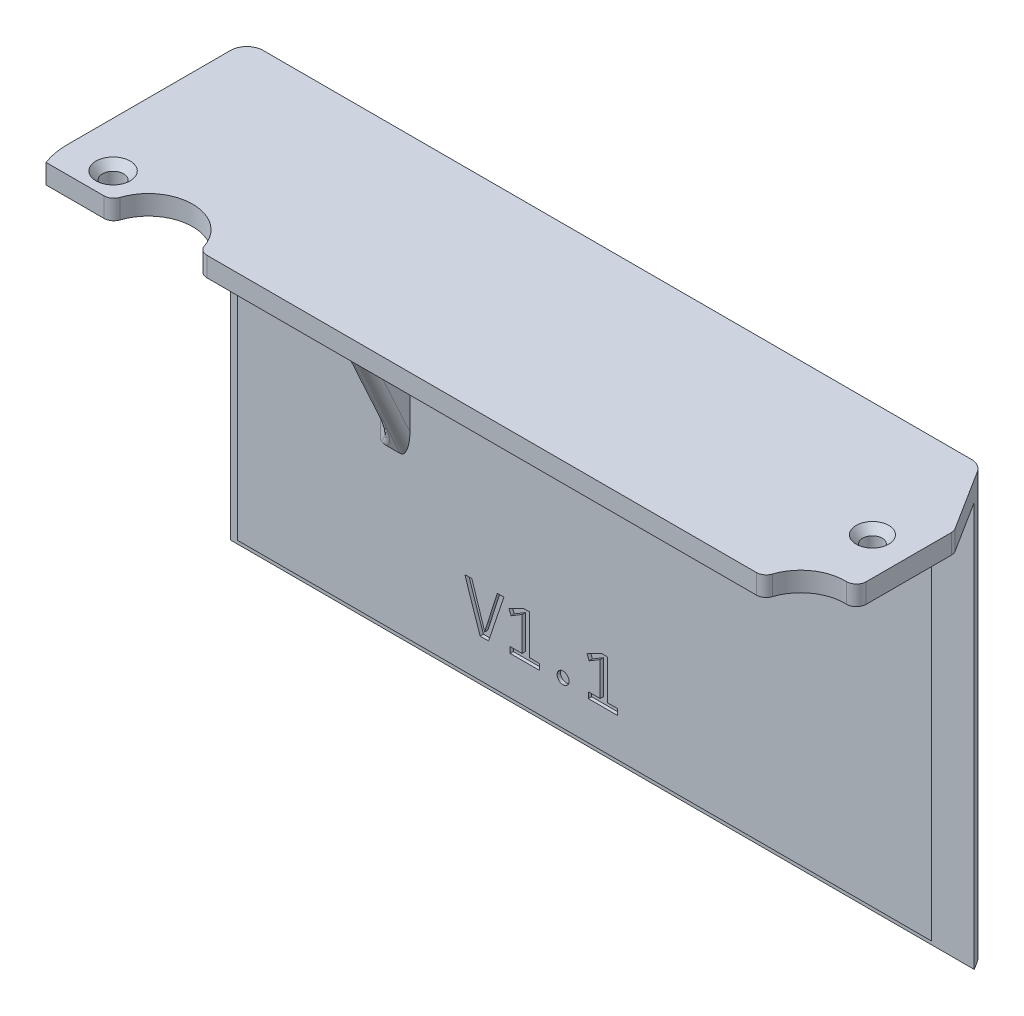
SolidWorks part; units mm, degrees
ref_plane "Front Plane" through (0, 0, 0) normal (0, 0, 1) x (1, 0, 0)
ref_plane "Top Plane" through (0, 0, 0) normal (0, 1, 0) x (1, 0, 0)
ref_plane "Right Plane" through (0, 0, 0) normal (1, 0, 0) x (0, 0, -1)
sketch "Sketch1" plane through (0, 0, 0) normal (0, 0, 1) x (1, 0, 0)
  line L1 (0, 0) -> (114, 0)
  line L2 (0, 0) -> (0, 65)
  line L3 (0, 65) -> (114, 65)
  line L4 (114, 0) -> (114, 65)
  dimension "D1" = 114
  dimension "D2" = 65
extrude "Boss-Extrude1" add sketch "Sketch1" along normal blind 2.5
sketch "Sketch2" plane through (0, 65, 0) normal (0, 1, 0) x (1, 0, 0)
  line L1 (114, -2.5) -> (0, -2.5) construction
  line L2 (110.2, -5) -> (3.3, -5)
  line L3 (3.3, -5) -> (5.8, -2.5)
  line L4 (107.7, -2.5) -> (110.2, -5)
  line L8 (5.8, -2.5) -> (107.7, -2.5)
  line L9 (0, -2.5) -> (0, 0) construction
  dimension "D1" = 2.5
  dimension "D3" = 45
  dimension "D4" = 45
  dimension "D5" = 5.8
  dimension "D6" = 6.3
extrude "Boss-Extrude2" add sketch "Sketch2" against normal offset from surface (62 mm away) 3 up to face at (57, 0, 1.25)
sketch "Sketch14" plane through (0, 65, 0) normal (0, 1, 0) x (1, 0, 0)
  line L0 (5.8, -2.5) -> (6.0828, -2.5)
  line L1 (6.0828, -2.5) -> (3.5828, -5)
  line L2 (3.3, -5) -> (110.2, -5) construction
  line L3 (3.5828, -5) -> (3.3, -5)
  line L4 (3.3, -5) -> (5.8, -2.5)
  line L5 (107.7, -2.5) -> (107.4172, -2.5)
  line L6 (107.4172, -2.5) -> (109.9172, -5)
  line L7 (109.9172, -5) -> (110.2, -5)
  line L8 (110.2, -5) -> (107.7, -2.5)
  dimension "D1" = 0.2
  dimension "D2" = 0.2
extrude "Cut-Extrude8" cut sketch "Sketch14" against normal through all
sketch "Sketch11" plane through (0, 65, 0) normal (0, 1, 0) x (1, 0, 0)
  line L0 (114, -2.5) -> (112.4226, 0)
  line L1 (114, 0) -> (0, 0) construction
  line L2 (112.4226, 0) -> (114, 0)
  line L3 (114, 0) -> (114, -2.5)
  dimension "D1" = 32.25
extrude "Cut-Extrude5" cut sketch "Sketch11" against normal through all
fillet "Fillet1" radius 2.5 2 edges at (0, 32.5, 0) (112.4226, 32.5, 0)
sketch "Sketch3" plane through (0, 65, 0) normal (0, 1, 0) x (1, 0, 0)
  line L0 (111.044, 0) -> (2.5, 0) construction
  line L1 (0, -2.5) -> (114, -2.5)
  line L2 (0, -2.5) -> (0, -31.5)
  line L3 (0, -31.5) -> (114, -31.5)
  line L4 (114, -2.5) -> (114, -31.5)
  line L5 (114, -2.5) -> (107.4172, -2.5) construction
  dimension "D1" = 31.5
extrude "Boss-Extrude3" add sketch "Sketch3" against normal blind 3
ref_plane "Plane1" through (30, 0, 0) normal (-1, 0, 0) x (0, 0, 1)
sketch "Sketch4" plane through (30, 0, 0) normal (-1, 0, 0) x (0, 0, 1)
  line L0 (21, 62) -> (5, 27)
  line L1 (2.5, 62) -> (31.5, 62) construction
  line L3 (5, 27) -> (5, 62)
  line L4 (5, 62) -> (21, 62)
  line L5 (5, 3) -> (5, 62) construction
  dimension "D1" = 35
  dimension "D2" = 16
extrude "Boss-Extrude4" add sketch "Sketch4" along normal blind 3
sketch "Sketch5" plane through (0, 62, 0) normal (0, -1, 0) x (1, 0, 0)
  line L0 (0, 2.5) -> (0, 31.5) construction
  line L1 (3.5828, 5) -> (21.5, 5)
  line L2 (3.5828, 5) -> (3.5828, 6.9)
  line L3 (3.5828, 6.9) -> (21.5, 6.9)
  line L4 (21.5, 5) -> (21.5, 6.9)
  line L5 (27, 5) -> (3.5828, 5) construction
  dimension "D1" = 21.5
  dimension "D2" = 1.9
extrude "Boss-Extrude5" add sketch "Sketch5" along normal blind 16
sketch "Sketch6" plane through (0, 65, 0) normal (0, 1, 0) x (1, 0, 0)
  line L0 (0, -29.5) -> (0, -31.75)
  line L1 (0, -31.75) -> (0.5349, -31.75)
  arc A0 (0, -29.5) -> (0.5349, -31.75) centre (5, -29.5) ccw construction
  arc A1 (0, -29.5) -> (0.5349, -31.75) centre (5, -29.5) ccw
extrude "Cut-Extrude1" cut sketch "Sketch6" against normal through all
sketch "Sketch7" plane through (0, 65, 0) normal (0, 1, 0) x (1, 0, 0)
  line L0 (119.5, -26.4153) -> (119.5, -31.75)
  line L1 (119.5, -31.75) -> (111.0558, -31.75)
  line L2 (11.0558, -31.75) -> (23.9442, -31.75)
  arc A1 (119.5, -26.4153) -> (111.0558, -31.75) centre (117.5, -32.6) ccw construction
  arc A2 (119.5, -26.4153) -> (111.0558, -31.75) centre (117.5, -32.6) ccw
  arc A3 (23.9442, -31.75) -> (11.0558, -31.75) centre (17.5, -32.6) ccw construction
  arc A4 (23.9442, -31.75) -> (11.0558, -31.75) centre (17.5, -32.6) ccw
extrude "Cut-Extrude2" cut sketch "Sketch7" against normal through all
sketch "Sketch8" plane through (0, 65, 0) normal (0, 1, 0) x (1, 0, 0)
  circle A0 centre (7, -27.5) radius 1.625
  dimension "D1" = 3.25
extrude "Cut-Extrude3" cut sketch "Sketch8" against normal through all
sketch "Sketch9" plane through (0, 65, 0) normal (0, 1, 0) x (1, 0, 0)
  line L0 (0.7174, -31.5) -> (0, -31.5)
  line L1 (0, -2.5) -> (0, -29.5) construction
  line L2 (0, -28) -> (0, -31.5)
  line L5 (114, -27.1228) -> (115.393, -26.1347)
  line L6 (110.8523, -31.1691) -> (110.781, -31.5)
  line L7 (111.0938, -31.5) -> (110.8523, -31.1691) construction
  line L8 (23.9062, -31.5) -> (111.0938, -31.5) construction
  line L10 (0.4174, -31.5) -> (11.0938, -31.5) construction
  line L11 (110.781, -31.5) -> (111.0938, -31.5)
  line L12 (11.0938, -31.5) -> (10.7896, -31.5)
  line L14 (23.9062, -31.5) -> (24.2104, -31.5)
  arc A0 (0, -28) -> (0.7174, -31.5) centre (11.9833, -27.3672) ccw
  arc A1 (23.9062, -31.5) -> (11.0938, -31.5) centre (17.5, -32.6) ccw construction
  arc A4 (23.9062, -31.5) -> (11.0938, -31.5) centre (17.5, -32.6) ccw
  arc A5 (114, -27.1228) -> (111.0938, -31.5) centre (117.5, -32.6) ccw construction
  arc A6 (114, -27.1228) -> (111.0938, -31.5) centre (117.5, -32.6) ccw
  arc A7 (115.393, -26.1347) -> (110.8523, -31.1691) centre (117.5, -32.6) ccw
  arc A8 (24.2104, -31.5) -> (10.7896, -31.5) centre (17.5, -32.6) ccw
  arc A9 (24.2019, -31.4492) -> (10.7981, -31.4492) centre (17.5, -32.6) ccw construction
  arc A10 (113.8385, -26.87) -> (110.7981, -31.4492) centre (117.5, -32.6) ccw construction
  dimension "D5" = 12
  dimension "D3" = 0.3
  dimension "D4" = 3.5
  dimension "D2" = 0.3
extrude "Cut-Extrude4" cut sketch "Sketch9" against normal blind 10
sketch "Sketch10" plane through (0, 62, 0) normal (0, -1, 0) x (1, 0, 0)
  line L0 (21.5, 6.9) -> (3.5828, 6.9) construction
  line L1 (0, 2.5) -> (6.8088, 2.5)
  line L2 (0, 2.5) -> (0, 6.9)
  line L3 (0, 6.9) -> (6.8088, 6.9)
  line L4 (6.8088, 2.5) -> (6.8088, 6.9)
extrude "Boss-Extrude6" add sketch "Sketch10" along normal blind 15.5
sketch "Sketch17" plane through (0, 0, 0) normal (-1, 0, 0) x (0, 0, 1)
  line L0 (5, 46) -> (6.9, 48.2643)
  line L1 (6.9, 46.5) -> (6.9, 62) construction
  line L2 (6.9, 48.2643) -> (6.9, 46)
  line L3 (6.9, 46) -> (5, 46) construction
  line L4 (6.9, 46) -> (5, 46)
  dimension "D1" = 50
extrude "Cut-Extrude10" cut sketch "Sketch17" against normal up to surface (21.5 mm away) up to face at (21.5, 54, 5.95)
sketch "Sketch12" plane through (0, 0, 5) normal (0, 0, 1) x (1, 0, 0)
  text T0 "V1.1" font "Consolas" height 7
extrude "Cut-Extrude6" cut sketch "Sketch12" against normal blind 0.5
sketch "Sketch13" plane through (0, 0, 0) normal (0, 0, -1) x (-1, 0, 0)
  text T0 "SCUTTLE\r\n11.1V LI-ION" font "SWTxt" height 8
extrude "Cut-Extrude7" cut sketch "Sketch13" against normal blind 0.3
sketch "Sketch15" plane through (0, 65, 0) normal (0, 1, 0) x (1, 0, 0)
  line L1 (114, -2.5) -> (114, -26.7699)
  line L2 (114, -2.5) -> (119.25, -10.8207)
  line L3 (119.25, -10.8207) -> (119.25, -26.029)
  line L4 (113.1583, -1.166) -> (114, -2.5) construction
  line L5 (117.5, -32.6) -> (117.5, -25.8) construction
  arc A0 (114, -26.7699) -> (119.25, -26.029) centre (117.5, -32.6) cw
  dimension "D1" = 1.75
extrude "Boss-Extrude7" add sketch "Sketch15" against normal up to surface (3 mm away) up to face at (7, 62, 29.125)
sketch "Sketch16" plane through (0, 65, 0) normal (0, 1, 0) x (1, 0, 0)
  line L0 (113.5, -17.6) -> (117.5, -32.6) construction
  circle A0 centre (113.5, -17.6) radius 1.5
  dimension "D1" = 3
  dimension "D2" = 15
  dimension "D3" = 4
extrude "Cut-Extrude9" cut sketch "Sketch16" against normal through all
fillet "Fillet3" radius 1.5 1 edges at (27, 44.5, 5)
fillet "Fillet2" radius 1.5 3 edges at (27, 46.1406, 13.75) (30, 44.5, 13) (26.5607, 27.9611, 5.4393)
fillet "Fillet4" radius 1.5 5 edges at (119.25, 63.5, 10.8207) (119.25, 63.5, 26.029) (110.781, 63.5, 31.5) (24.2104, 63.5, 31.5) (10.7896, 63.5, 31.5)
chamfer "Chamfer1" distance 1 angle 50 2 edges at (7, 65, 29.125) (113.5, 65, 19.1) first distance on face at (113.5, 65, 19.1)
